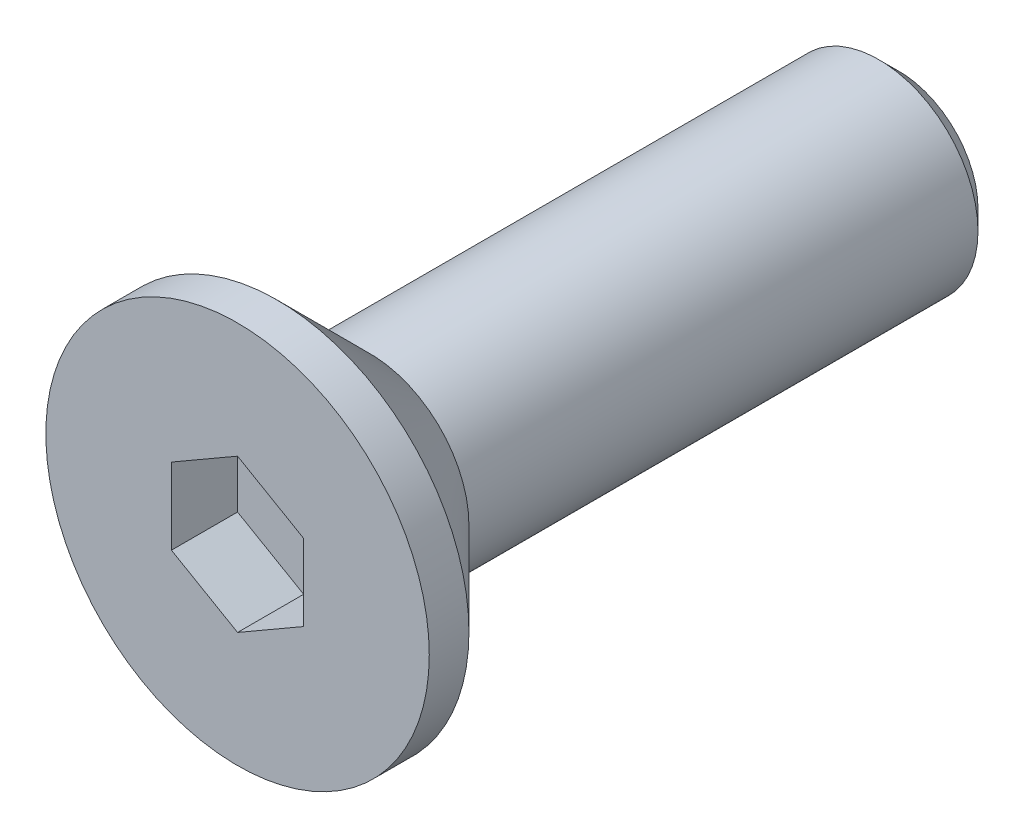
SolidWorks part; units mm, degrees
material "1.4000 (X6Cr13)"
ref_plane "Ebene vorne" through (0, 0, 0) normal (0, 0, 1) x (1, 0, 0)
ref_plane "Ebene oben" through (0, 0, 0) normal (0, 1, 0) x (1, 0, 0)
ref_plane "Ebene rechts" through (0, 0, 0) normal (1, 0, 0) x (0, 0, -1)
sketch "Skizze1" plane through (0, 0, 0) normal (1, 0, 0) x (0, 0, -1)
  line L0 (-31.7636, 0) -> (42.9935, 0) construction
  line L1 (0, 26.0256) -> (0, -29.3045) construction
  line L2 (0, 0) -> (0, 2.9)
  line L3 (0.6, 2.9) -> (2, 1.5)
  line L4 (2, 1.5) -> (10, 1.5)
  line L5 (10, 1.5) -> (10, 0)
  line L6 (10, 0) -> (0, 0)
  line L7 (0, 2.9) -> (0.6, 2.9)
  dimension "D1" = 3
  dimension "D2" = 10
  dimension "D3" = 5.8
  dimension "D4" = 45
  dimension "D5" = 2
  dimension "D6" = 0.6
revolve "Rotation1" add sketch "Skizze1" angle 360 about L0
sketch "Skizze3" plane through (0, 0, 0) normal (0, 0, 1) x (1, 0, 0)
  line L0 (0, 1.5356) -> (0, -1.3958) construction
  line L1 (-1.5297, 0) -> (1.3792, 0) construction
  line L3 (1, -0.5774) -> (1, 0.5774)
  line L4 (1, 0.5774) -> (0, 1.1547)
  line L5 (0, 1.1547) -> (-1, 0.5774)
  line L6 (-1, 0.5774) -> (-1, -0.5774)
  line L7 (-1, -0.5774) -> (0, -1.1547)
  line L8 (0, -1.1547) -> (1, -0.5774)
  circle A0 centre (0, 0) radius 1 construction
  dimension "D1" = 2
extrude "Schnitt-Linear austragen1" cut sketch "Skizze3" against normal blind 1
chamfer "Fase1" distance 0.3 angle 45 1 edges at (1.5, 0, -10)
ref_axis "Achse1" through (0, 0, 0.3) along (0, 0, -1)
